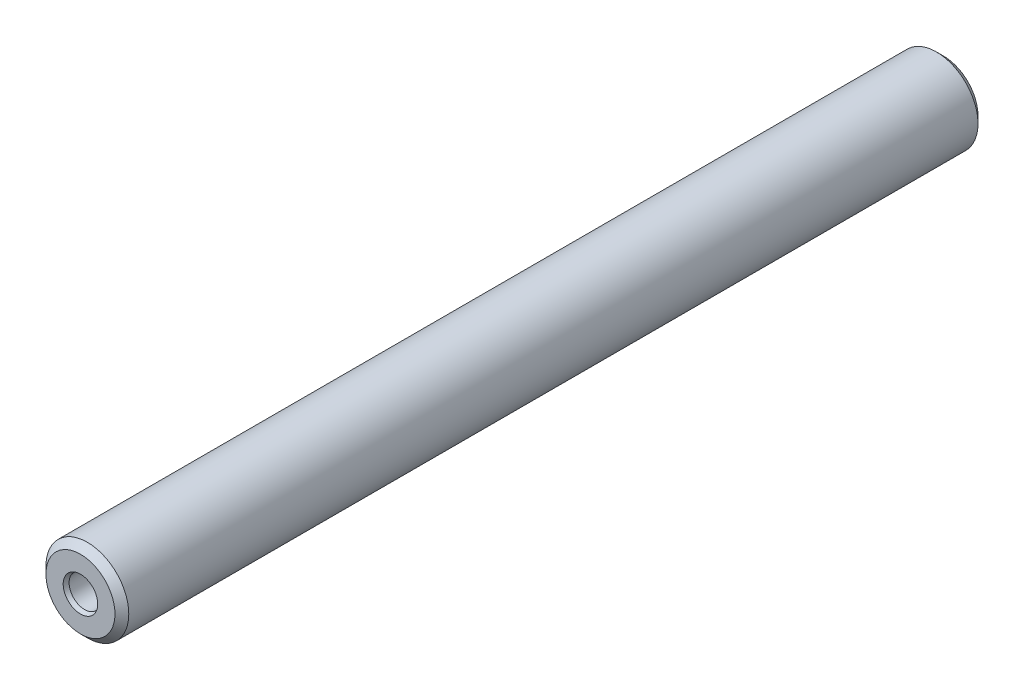
SolidWorks part; units mm, degrees
ref_plane "Plan de face" through (0, 0, 0) normal (0, 0, 1) x (1, 0, 0)
ref_plane "Plan de dessus" through (0, 0, 0) normal (0, 1, 0) x (1, 0, 0)
ref_plane "Plan de droite" through (0, 0, 0) normal (1, 0, 0) x (0, 0, -1)
sketch "Esquisse1" plane through (0, 0, 0) normal (0, 0, 1) x (1, 0, 0)
  circle A0 centre (0, 0) radius 6
extrude "Extrusion1" add sketch "Esquisse1" along normal blind 125
chamfer "Chanfrein1" distance 1 angle 45 2 edges at (6, 0, 0) (6, 0, 125)
hole_wizard "Dégagement M41" positions "Esquisse3D1" profile "Esquisse4" hole size "M4" standard "Ansi Métrique"
sketch3d "Esquisse3D1"
  line L0 (0, 0, 124) -> (0, 0, 125) construction
  point P0 (0, 0, 125)
  point P4 (0, 0, 0)
sketch "Esquisse4" plane through (0, 0, 125) normal (1, 0, 0) x (0, -1, 0)
  line L0 (0, 0) -> (0, 12.3519)
  line L1 (0, 12.3519) -> (2.25, 11)
  line L2 (2.25, 11) -> (2.25, 0.6036)
  line L3 (2.25, 0.6036) -> (2.5, 0)
  line L5 (2.5, 0) -> (0, 0)
  line L6 (-2.25, 0.6036) -> (-2.5, 0) construction
  line L10 (0, 12.3519) -> (-2.25, 11) construction
  line L11 (0, -6.35) -> (0, 107.95) construction
  dimension "Diamètre du perçage" = 4.5
  dimension "Profondeur du perçage" = 11
  dimension "Diamètre du fraisage entrant" = 5
  dimension "Angle du fraisage entrant" = 45
  dimension "Angle de pointe" = 118
hole_wizard "Dégagement M42" positions "Esquisse3D5" profile "Esquisse9" hole size "M4" standard "Ansi Métrique"
sketch3d "Esquisse3D5"
  point P0 (0, 0, 0)
  point P3 (0, 0, 0)
  point P5 (0, 0, 0)
sketch "Esquisse9" plane through (0, 0, 0) normal (1, 0, 0) x (0, 1, 0)
  line L0 (0, 0) -> (0, 12.3519)
  line L1 (0, 12.3519) -> (2.25, 11)
  line L2 (2.25, 11) -> (2.25, 0.6036)
  line L3 (2.25, 0.6036) -> (2.5, 0)
  line L5 (2.5, 0) -> (0, 0)
  line L6 (-2.25, 0.6036) -> (-2.5, 0) construction
  line L10 (0, 12.3519) -> (-2.25, 11) construction
  line L11 (0, -6.35) -> (0, 107.95) construction
  dimension "Diamètre du perçage" = 4.5
  dimension "Profondeur du perçage" = 11
  dimension "Diamètre du fraisage entrant" = 5
  dimension "Angle du fraisage entrant" = 45
  dimension "Angle de pointe" = 118
